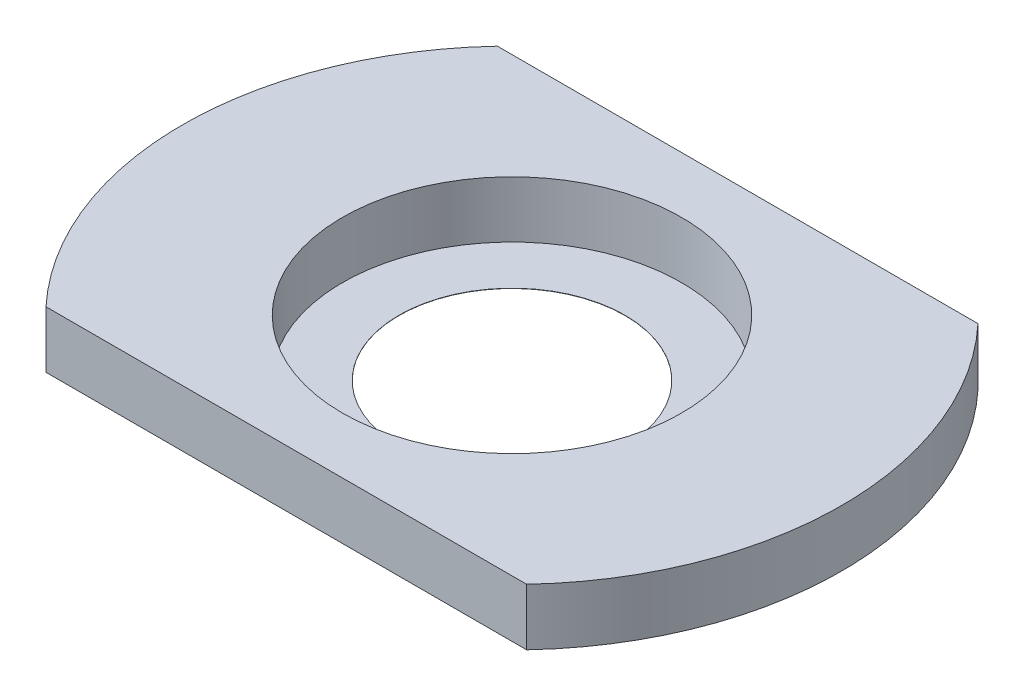
SolidWorks part; units mm, degrees
material "1345 Alloy"
ref_plane "Front Plane" through (0, 0, 0) normal (0, 0, 1) x (1, 0, 0)
ref_plane "Top Plane" through (0, 0, 0) normal (0, 1, 0) x (1, 0, 0)
ref_plane "Right Plane" through (0, 0, 0) normal (1, 0, 0) x (0, 0, -1)
sketch "Sketch1" plane through (0, 0, 0) normal (0, 1, 0) x (1, 0, 0)
  circle A0 centre (0, 0) radius 1750
extrude "Boss-Extrude1" add sketch "Sketch1" along normal blind 500
sketch "Sketch2" plane through (0, 500, 0) normal (0, 1, 0) x (1, 0, 0)
  circle A0 centre (0, 0) radius 900
extrude "Cut-Extrude2" cut sketch "Sketch2" against normal blind 300
sketch "Sketch9" plane through (0, 0, 0) normal (0, -1, 0) x (1, 0, 0)
  line L1 (-2106.3119, -1198.0599) -> (2106.3119, -1198.0599)
  line L2 (-2106.3119, -1198.0599) -> (-2106.3119, 1198.0599)
  line L3 (-2106.3119, 1198.0599) -> (2106.3119, 1198.0599)
  line L4 (2106.3119, -1198.0599) -> (2106.3119, 1198.0599)
  line L5 (-2106.3119, -1198.0599) -> (2106.3119, 1198.0599) construction
  line L6 (-2106.3119, 1198.0599) -> (2106.3119, -1198.0599) construction
  line L7 (-2636.6179, -2082.9122) -> (2636.6179, -2082.9122)
  line L8 (-2636.6179, -2082.9122) -> (-2636.6179, 2082.9122)
  line L9 (-2636.6179, 2082.9122) -> (2636.6179, 2082.9122)
  line L10 (2636.6179, -2082.9122) -> (2636.6179, 2082.9122)
  line L11 (-2636.6179, -2082.9122) -> (2636.6179, 2082.9122) construction
  line L12 (-2636.6179, 2082.9122) -> (2636.6179, -2082.9122) construction
  point P0 (0, 0)
  point P6 (0, 0)
extrude "Cut-Extrude10" cut sketch "Sketch9" against normal through all both and the other way through all
sketch "Sketch3" plane through (0, 0, 0) normal (0, -1, 0) x (1, 0, 0)
  circle A0 centre (0, 0) radius 600
extrude "Cut-Extrude3" cut sketch "Sketch3" against normal blind 300
shell "Shell1" thickness 1.5 removed face at (0, 0, -600)
sketch "Sketch10" plane through (0, 198.5, 0) normal (0, -1, 0) x (1, 0, 0)
  line L1 (2226.5426, -1551.0392) -> (-2226.5426, -1551.0392)
  line L2 (2226.5426, -1551.0392) -> (2226.5426, 1551.0392)
  line L3 (2226.5426, 1551.0392) -> (-2226.5426, 1551.0392)
  line L4 (-2226.5426, -1551.0392) -> (-2226.5426, 1551.0392)
  line L5 (2226.5426, -1551.0392) -> (-2226.5426, 1551.0392) construction
  line L6 (2226.5426, 1551.0392) -> (-2226.5426, -1551.0392) construction
  point P0 (0, 0)
extrude "Cut-Extrude11" cut sketch "Sketch10" along normal through all
